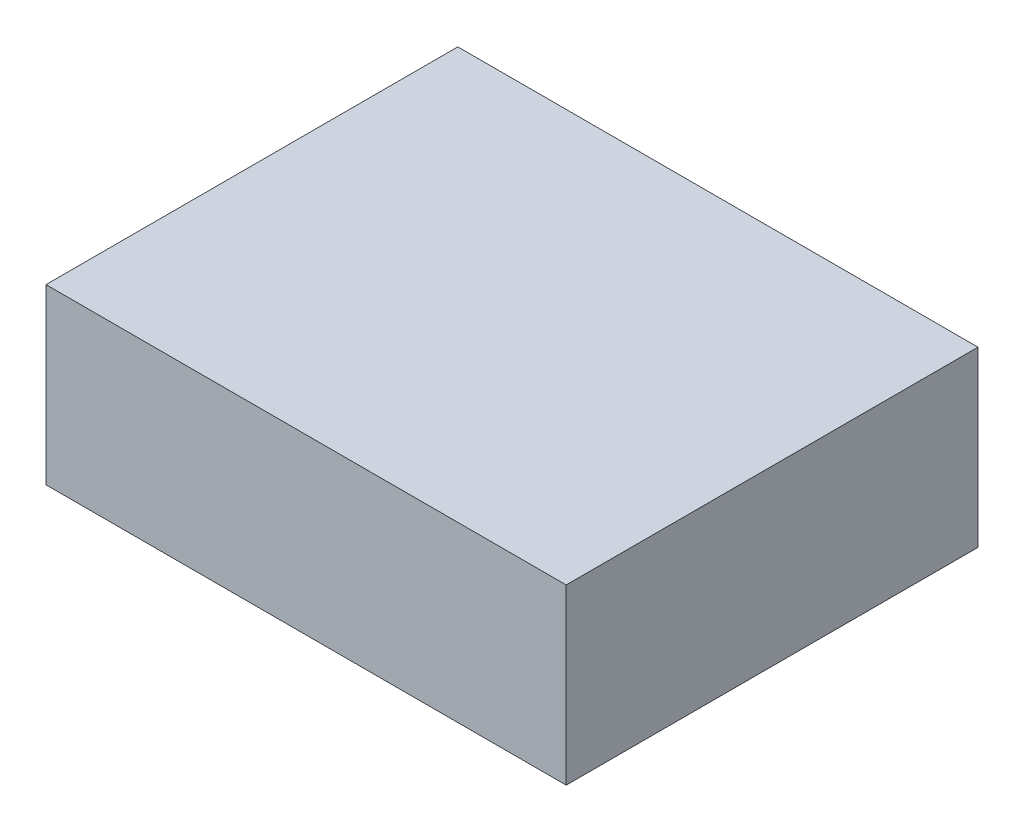
SolidWorks part; units mm, degrees
ref_plane "Front Plane" through (0, 0, 0) normal (0, 0, 1) x (1, 0, 0)
ref_plane "Top Plane" through (0, 0, 0) normal (0, 1, 0) x (1, 0, 0)
ref_plane "Right Plane" through (0, 0, 0) normal (1, 0, 0) x (0, 0, -1)
sketch "SK_Envelope" plane through (0, 0, 0) normal (0, 1, 0) x (1, 0, 0)
  line L1 (-60, 47.5) -> (60, 47.5)
  line L2 (-60, 47.5) -> (-60, -47.5)
  line L3 (-60, -47.5) -> (60, -47.5)
  line L4 (60, 47.5) -> (60, -47.5)
  dimension "D1" = 95
  dimension "D2" = 120
  dimension "D3" = 47.5
  dimension "D4" = 60
extrude "EX_Envelope" add sketch "SK_Envelope" along normal blind 40
ref_axis "AX_X" through (0, 0, -52.25) along (0, 0, 1)
ref_axis "AX_Y" through (66, 0, 0) along (-1, 0, 0)
ref_axis "AX_Z" through (0, 42, 0) along (0, -1, 0)
equation "\"BODY_L\"= 420"
equation "\"BODY_W\"= 340"
equation "\"FLOOR_Z\"= 35"
equation "\"DECK_Z\"= 180"
equation "\"DECK_T\"= 2"
equation "\"GRID\"= 20"
equation "\"PROFILE\"= 20"
equation "\"SM_T\"= 1.5"
equation "\"PAN_T\"= 1.5"
equation "\"PAN_TOP\"= \"FLOOR_Z\" + \"PAN_T\""
equation "\"RAIL_Y\"= 140"
equation "\"RAIL_X\"= \"BODY_L\" / 2 - \"PROFILE\" / 2 - 2"
equation "\"BOTRING_Z\"= \"PAN_TOP\" + \"PROFILE\" / 2"
equation "\"TOPRING_Z\"= \"DECK_Z\" - \"DECK_T\" - \"PROFILE\" / 2"
equation "\"DRAWER_Z\"= 93"
equation "\"MIDX_Z\"= \"DRAWER_Z\" - \"SM_T\" - \"PROFILE\" / 2"
equation "\"SKIN_Y\"= \"RAIL_Y\" + \"PROFILE\" / 2"
equation "\"SKIN_T\"= 2"
equation "\"WHEEL_D\"= 144"
equation "\"WHEEL_W\"= 52"
equation "\"TRACK\"= 365"
equation "\"AXLE_Z\"= \"WHEEL_D\" / 2"
equation "\"WHEEL_WEB_OFF\"= 6"
equation "\"HUB_T\"= 8"
equation "\"BUSHING_L\"= 6"
equation "\"HUB_GAP\"= 1"
equation "\"MOTOR_UP\"= 7"
equation "\"MOTOR_FACE_Y\"= \"TRACK\" / 2 + \"WHEEL_WEB_OFF\" - (\"BUSHING_L\" + \"HUB_GAP\" + \"HUB_T\")"
equation "\"MOTOR_AXIS_Z\"= \"AXLE_Z\" + \"MOTOR_UP\""
equation "\"CASTER_D\"= 50"
equation "\"CASTER_X\"= 150"
equation "\"CASTER_H\"= 68"
equation "\"POST_X\"= -40"
equation "\"POST_DY\"= 120"
equation "\"POST_SIZE\"= 20"
equation "\"POST_TOP\"= 400"
equation "\"BRACE_Z\"= 335"
equation "\"STRUT_X0\"= -140"
equation "\"HEAD_X0\"= -110"
equation "\"HEAD_X1\"= 12"
equation "\"BEZEL_T\"= 3"
equation "\"WEDGE_MID\"= 7.7"
equation "\"OAK_D\"= 22.9"
equation "\"HEAD_W\"= 210"
equation "\"HEAD_Z0\"= \"POST_TOP\""
equation "\"HEAD_TOP\"= 525"
equation "\"HEAD_TOP_X\"= -20"
equation "\"SCREEN_ANG\"= 35"
equation "\"LENS_X\"= 45.6"
equation "\"LENS_Z\"= 450"
equation "\"OAK_TILT\"= 5"
equation "\"OAK_VFOV_DEPTH\"= 79.5"
equation "\"OAK_VFOV_RGB\"= 72"
equation "\"LIDAR_X\"= 110"
equation "\"SCAN_Z\"= 260"
equation "\"STRUT_Z\"= \"SCAN_Z\" - 20"
equation "\"LIDAR_SCAN_H\"= 27.2"
equation "\"LIDAR_MOUNT_Z\"= \"SCAN_Z\" - \"LIDAR_SCAN_H\""
equation "\"ESTOP_X\"= -172.5"
equation "\"ESTOP_Y\"= -127.5"
equation "\"ESTOP_TOP\"= 225"
equation "\"BUMPER_T\"= 15"
equation "\"BUMPER_Z0\"= 40"
equation "\"BUMPER_Z1\"= 130"
equation "\"CLIFF_X\"= 218"
equation "\"CLIFF_Y\"= 105"
equation "\"CLIFF_Z\"= 72"
equation "\"CLIFF_ANG\"= 50"
equation "\"CONTACT_X\"= 216"
equation "\"CONTACT_Y\"= 64"
equation "\"CONTACT_Z\"= 30"
equation "\"DOCK_TAG_DIST\"= 250"
equation "\"DOCK_TAG_SIZE\"= 80"
equation "\"DOCK_TAG_Z\"= 400"
equation "\"BAT_L\"= 240"
equation "\"BAT_W\"= 90"
equation "\"BAT_H\"= 58"
equation "\"BAT_Z\"= \"DRAWER_Z\" + \"SM_T\""
equation "\"BAT_X\"= 0"
equation "\"PCB_L\"= 95"
equation "\"PCB_W\"= 120"
equation "\"PCB_H\"= 40"
equation "\"PCB_X\"= 62.5"
equation "\"DRV_X\"= 85"
equation "\"DRV_Y\"= 100"
equation "\"DRV_S\"= 50"
equation "\"COMPUTE_X\"= -65"
equation "\"COMPUTE_L\"= 90"
equation "\"COMPUTE_W\"= 160"
equation "\"D1@SK_Envelope\" = \"PCB_L\""
equation "\"D2@SK_Envelope\" = \"PCB_W\""
equation "\"D3@SK_Envelope\" = (\"PCB_L\") / 2"
equation "\"D4@SK_Envelope\" = (\"PCB_W\") / 2"
equation "\"D1@EX_Envelope\" = \"PCB_H\""
